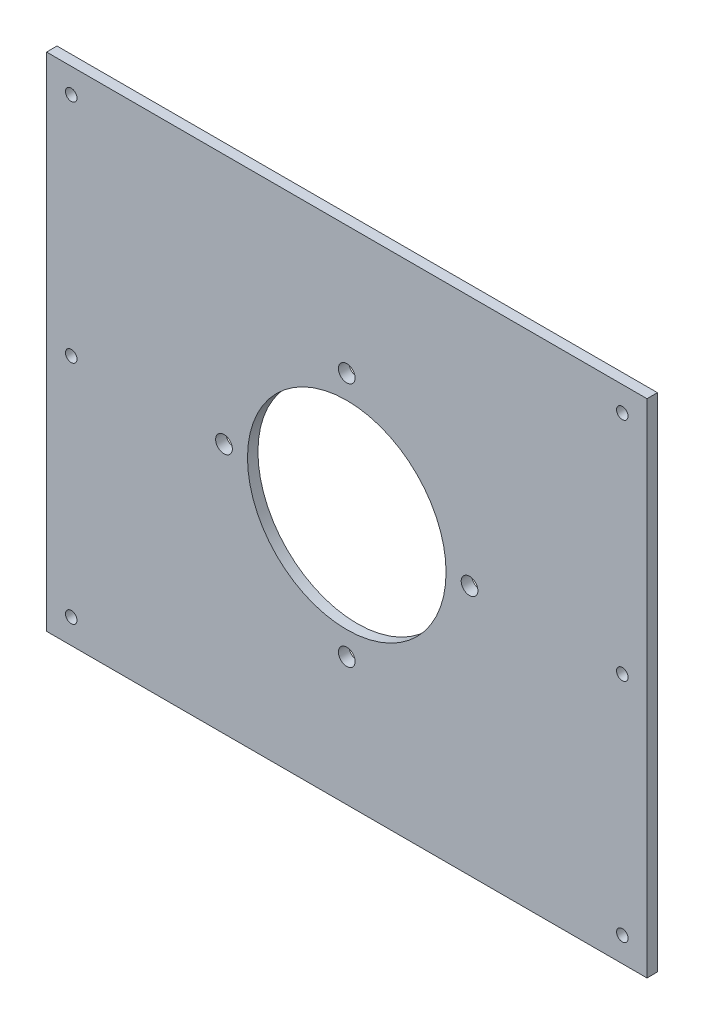
SolidWorks part; units mm, degrees
ref_plane "Front Plane" through (0, 0, 0) normal (0, 0, 1) x (1, 0, 0)
ref_plane "Top Plane" through (0, 0, 0) normal (0, 1, 0) x (1, 0, 0)
ref_plane "Right Plane" through (0, 0, 0) normal (1, 0, 0) x (0, 0, -1)
sketch "Sketch1" plane through (0, 0, 0) normal (0, 0, 1) x (1, 0, 0)
  line L0 (-80.2008, -94.5008) -> (284.5992, 210.2992) construction
  line L1 (-80.2008, -94.5008) -> (284.5992, -94.5008)
  line L2 (-80.2008, -94.5008) -> (-80.2008, 210.2992)
  line L3 (-80.2008, 210.2992) -> (284.5992, 210.2992)
  line L4 (284.5992, -94.5008) -> (284.5992, 210.2992)
  circle A0 centre (102.1992, 57.8992) radius 60.325
  circle A1 centre (102.1992, 57.8992) radius 74.6
  circle A2 centre (102.1992, 132.4992) radius 5.08
  circle A3 centre (27.5992, 57.8992) radius 5.08
  circle A4 centre (102.1992, -16.7008) radius 5.08
  circle A5 centre (176.7992, 57.8992) radius 5.08
  circle A6 centre (-65.2008, 195.2992) radius 3.5
  circle A7 centre (-65.2008, 57.8992) radius 3.5
  circle A8 centre (-65.2008, -79.5008) radius 3.5
  circle A9 centre (269.5992, 195.2992) radius 3.5
  circle A10 centre (269.5992, 57.8992) radius 3.5
  circle A11 centre (269.5992, -79.5008) radius 3.5
  point P11 (102.1992, 57.8992)
  dimension "D3" = 120.65
  dimension "D6" = 149.2
  dimension "D7" = 10.16
  dimension "D8" = 10.16
  dimension "D9" = 10.16
  dimension "D10" = 10.16
  dimension "D11" = 7
  dimension "D14" = 7
  dimension "D17" = 7
  dimension "D20" = 7
  dimension "D23" = 7
  dimension "D26" = 7
  dimension "D1" = 364.8
  dimension "D2" = 304.8
  dimension "D4" = 0
  dimension "D5" = 0
  dimension "D12" = 15
  dimension "D13" = 15
  dimension "D15" = 15
  dimension "D16" = 152.4
  dimension "D18" = 15
  dimension "D19" = 15
  dimension "D21" = 15
  dimension "D22" = 15
  dimension "D24" = 15
  dimension "D25" = 152.4
  dimension "D27" = 15
  dimension "D28" = 15
extrude "Boss-Extrude1" add sketch "Sketch1" along normal blind 6.35 contours L0 L1 L4 A9 A1 A5 A4 A8 A11 A10 | L2 L0 A8 A1 A3 A2 A9 L3 A6 A7 | A1 L0 A0 A2 A3 | L0 A1 A4 A5 A0 region at (33.9879, 113.7729, 0) region at (170.4106, 2.0256, 0) region at (34.6455, 30.7551, 0) region at (51.581, 13.265, 0)
equation "\"D16@Sketch1\"=\"D2@Sketch1\"/2"
equation "\"D25@Sketch1\"=\"D2@Sketch1\"/2"
